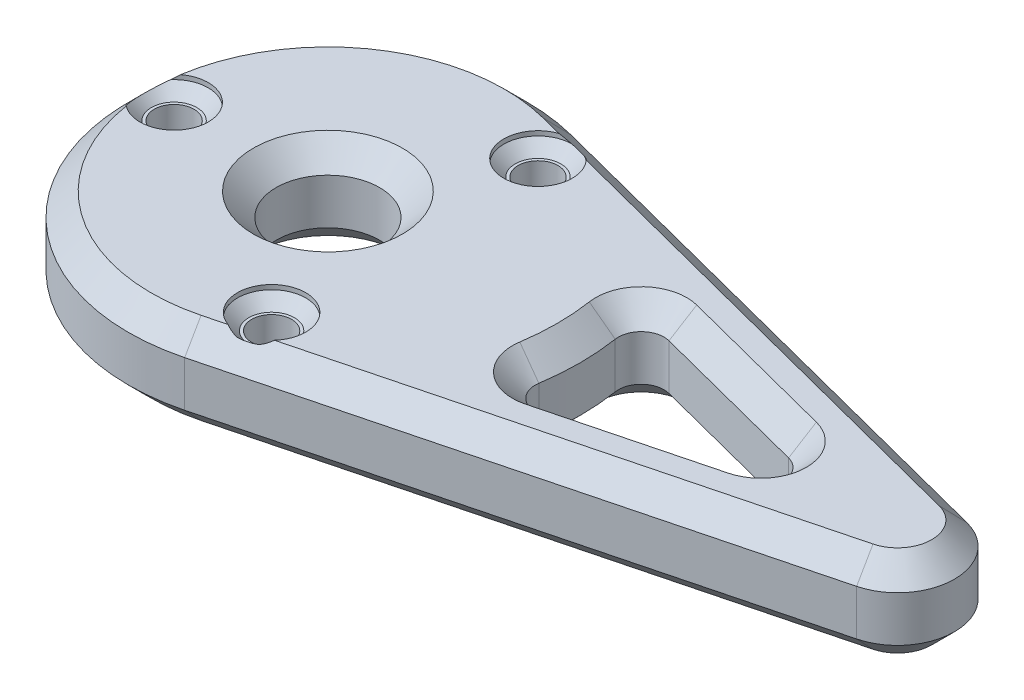
SolidWorks part; units mm, degrees
ref_plane "Front Plane" through (0, 0, 0) normal (0, 0, 1) x (1, 0, 0)
ref_plane "Top Plane" through (0, 0, 0) normal (0, 1, 0) x (1, 0, 0)
ref_plane "Right Plane" through (0, 0, 0) normal (1, 0, 0) x (0, 0, -1)
sketch "Sketch1" plane through (0, 0, 0) normal (0, 1, 0) x (1, 0, 0)
  line L0 (4.375, 16.9443) -> (51.25, 4.8412)
  line L1 (-45.5871, 0) -> (110.9335, 0) construction
  line L2 (4.375, -16.9443) -> (51.25, -4.8412)
  line L3 (6.75, 11.6913) -> (-13.5, 0) construction
  line L4 (-13.5, 0) -> (6.75, -11.6913) construction
  line L5 (6.75, -11.6913) -> (6.75, 11.6913) construction
  arc A0 (4.375, 16.9443) -> (4.375, -16.9443) centre (0, 0) ccw
  arc A1 (51.25, -4.8412) -> (51.25, 4.8412) centre (50, 0) ccw
  circle A2 centre (0, 0) radius 13.5 construction
  circle A3 centre (6.75, 11.6913) radius 1.75
  circle A4 centre (-13.5, 0) radius 1.75
  circle A5 centre (6.75, -11.6913) radius 1.75
  point P16 (51.25, -4.8412)
  point P17 (0, 0)
  point P18 (-13.1483, -3.0615)
  point P19 (0, 11.3711)
  point P20 (0, 8.9351)
  point P21 (6.9952, 11.5463)
  point P22 (-13.5, 0)
  dimension "D1" = 27
  dimension "D2" = 3.5
  dimension "D4" = 17.5
  dimension "D5" = 5
  dimension "D3" = 50
extrude "Boss-Extrude1" add sketch "Sketch1" along normal blind 8
sketch "Sketch2" plane through (0, 8, 0) normal (0, 1, 0) x (1, 0, 0)
  circle A0 centre (6.75, -11.6913) radius 3
  circle A1 centre (6.75, 11.6913) radius 3
  circle A2 centre (-13.5, 0) radius 3
  dimension "D1" = 6
extrude "Cut-Extrude1" cut sketch "Sketch2" against normal blind 1.4
sketch "Sketch3" plane through (0, 8, 0) normal (0, 1, 0) x (1, 0, 0)
  line L4 (2.875, -11.1348) -> (46, 0)
  line L5 (46, 0) -> (2.875, 11.1348)
  line L6 (21.1758, -6.4096) -> (46, 0)
  line L7 (46, 0) -> (21.1758, 6.4096)
  arc A2 (21.1758, -6.4096) -> (21.1758, 6.4096) centre (0, 0) ccw
  arc A4 (2.875, 11.1348) -> (2.875, -11.1348) centre (0, 0) ccw
  dimension "D1" = 6
extrude "Cut-Extrude2" cut sketch "Sketch3" against normal through all
fillet "Fillet1" radius 2 3 edges at (46, 4, 0) (21.1758, 4, 6.4096) (21.1758, 4, -6.4096)
chamfer "Chamfer1" distance 1 angle 45 3 edges at (6.75, 6.6, 14.6913) (-13.5, 6.6, 3) (6.75, 6.6, -8.6913)
sketch "Sketch4" plane through (0, 8, 0) normal (0, 1, 0) x (1, 0, 0)
  circle A0 centre (0, 0) radius 4.5416
extrude "Cut-Extrude3" cut sketch "Sketch4" against normal through all
chamfer "Chamfer2" distance 2 angle 45 19 edges at (40, 0, 0) (31.4231, 0, -3.7637) (31.4231, 0, 3.7637) (22.5049, 0, -5.138) (22.5049, 0, 5.138) (22.1246, 0, 0) (22.5049, 8, -5.138) (22.1246, 8, 0) (31.4231, 8, -3.7637) (22.5049, 8, 5.138) (40, 8, 0) (31.4231, 8, 3.7637) (27.8125, 0, -10.8928) (-17.5, 0, 0) (55, 0, 0) (27.8125, 0, 10.8928) (55, 8, 0) (0, 0, 4.5416) (0, 8, 4.5416)
